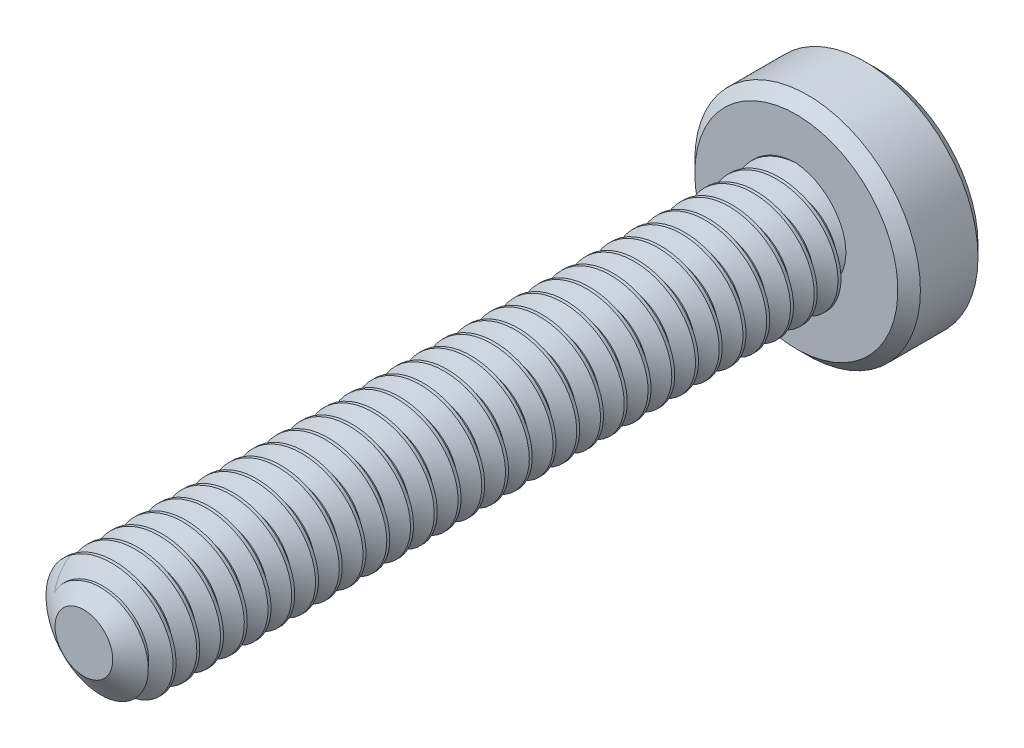
SolidWorks part; units mm, degrees
other "DetailItem1"
ref_plane "Front Plane" through (0, 0, 0) normal (0, 0, 1) x (1, 0, 0)
ref_plane "Top Plane" through (0, 0, 0) normal (0, 1, 0) x (1, 0, 0)
ref_plane "Right Plane" through (0, 0, 0) normal (1, 0, 0) x (0, 0, -1)
sketch "Sketch1" plane through (0, 0, 0) normal (0, 0, 1) x (1, 0, 0)
  circle A0 centre (0, 0) radius 1
  dimension "OD" = 2
extrude "Extrude1" add sketch "Sketch1" against normal blind 12
sketch "Sketch2" plane through (0, 0, 0) normal (0, 0, 1) x (1, 0, 0)
  circle A0 centre (0, 0) radius 1 construction
  circle A1 centre (0, 0) radius 1
curve "Helix/Spiral1" pitch 0.4 height 12.4 turns 31 parameters "pitch"=0.4
sketch "Sketch3" plane through (0, 0, 0) normal (1, 0, 0) x (0, 0, -1)
  line L0 (-0.35, 1) -> (-0.2, 0.7402)
  line L1 (-0.2, 0.7402) -> (-0.15, 0.7402)
  line L2 (-0.15, 0.7402) -> (0, 1)
  line L3 (-0.35, 1) -> (0, 1)
  line L4 (-0.175, 1) -> (-0.175, 0.7402) construction
  line L5 (-0.275, 0.8701) -> (-0.075, 0.8701) construction
  line L6 (0, 1) -> (0, -1) construction
  dimension "D1" = 0.05
  dimension "D2" = 0.2
  dimension "D3" = 60
sweep "Cut-Sweep1" cut profiles "Sketch3" path "Helix/Spiral1" align with end faces yes
sketch "Sketch4" plane through (0, 0, 0) normal (1, 0, 0) x (0, 0, -1)
  line L0 (0.3598, 1) -> (0, 0.4862)
  line L1 (0, 0.4862) -> (0, 1)
  line L2 (0.3598, 1) -> (0, 1)
  line L3 (-0.35, 1) -> (0, 1) construction
  line L4 (0, 0) -> (7.0209, 0) construction
  dimension "D1" = 55
  dimension "D2" = 0.254
revolve "Cut-Revolve1" cut sketch "Sketch4" angle 360 about L4
sketch "Sketch6" plane through (0, 0, -12) normal (0, 0, -1) x (-1, 0, 0)
  circle A0 centre (0, 0) radius 1.9
  dimension "head dia" = 3.8
extrude "Extrude2" add sketch "Sketch6" along normal blind 1.35
sketch "Sketch7" plane through (0, 0, -13.35) normal (0, 0, -1) x (-1, 0, 0)
  line L1 (0, 0.7506) -> (-0.65, 0.3753)
  line L2 (-0.65, 0.3753) -> (-0.65, -0.3753)
  line L3 (-0.65, -0.3753) -> (0, -0.7506)
  line L4 (0, -0.7506) -> (0.65, -0.3753)
  line L5 (0.65, -0.3753) -> (0.65, 0.3753)
  line L6 (0.65, 0.3753) -> (0, 0.7506)
  circle A0 centre (0, 0) radius 0.65 construction
  dimension "hex dia" = 1.3
extrude "Cut-Extrude1" cut sketch "Sketch7" against normal blind 0.975
sketch "Sketch8" plane through (0, 0, -13.35) normal (0, 0, -1) x (-1, 0, 0)
  circle A0 centre (0, 0) radius 0.7506
extrude "Cut-Extrude2" cut sketch "Sketch8" against normal through all draft 45
chamfer "Chamfer1" distance 0.19 angle 45 2 edges at (-1.9, 0, -13.35) (-1.9, 0, -12)
sketch "Sketch10" plane through (0, 0, -12) normal (0, 0, 1) x (1, 0, 0)
  circle A1 centre (0, 0) radius 1
  circle A2 centre (0, 0) radius 1
  dimension "D1" = 0
ref_plane "Plane1" through (0, 0, -30) normal (0, 0, 1) x (1, 0, 0)
extrude "partial thread" [suppressed] add sketch "Sketch10" along normal up to surface (10 mm away) separate body
chamfer "Chamfer2" [suppressed] distance 0.04 angle 45
combine bodies "Combine1" [suppressed] operation type add bodies to combine 107 108
sketch "Sketch9" plane through (0, 0, 0) normal (1, 0, 0) x (0, 0, -1)
  line L0 (0, 1) -> (0, -1) construction
  line L1 (1, 1) -> (1, -1) construction
  dimension "D1" = 1
equation "\"D3@Helix/Spiral1\" = \"screw length@Extrude1\"+\"pitch@Helix/Spiral1\""
equation "\"D1@Sketch3\" = \"pitch@Helix/Spiral1\"*.125"
equation "\"D2@Sketch3\" = \"pitch@Helix/Spiral1\"*.5"
equation "\"D1@Cut-Extrude1\" = \"hex dia@Sketch7\"*.75"
equation "\"D1@Chamfer1\" = \"head dia@Sketch6\"*.05"
equation "\"D1@Sketch9\" = \"pitch@Helix/Spiral1\"*2.5"
equation "\"D1@Chamfer2\"=\"OD@Sketch1\"*.02"
